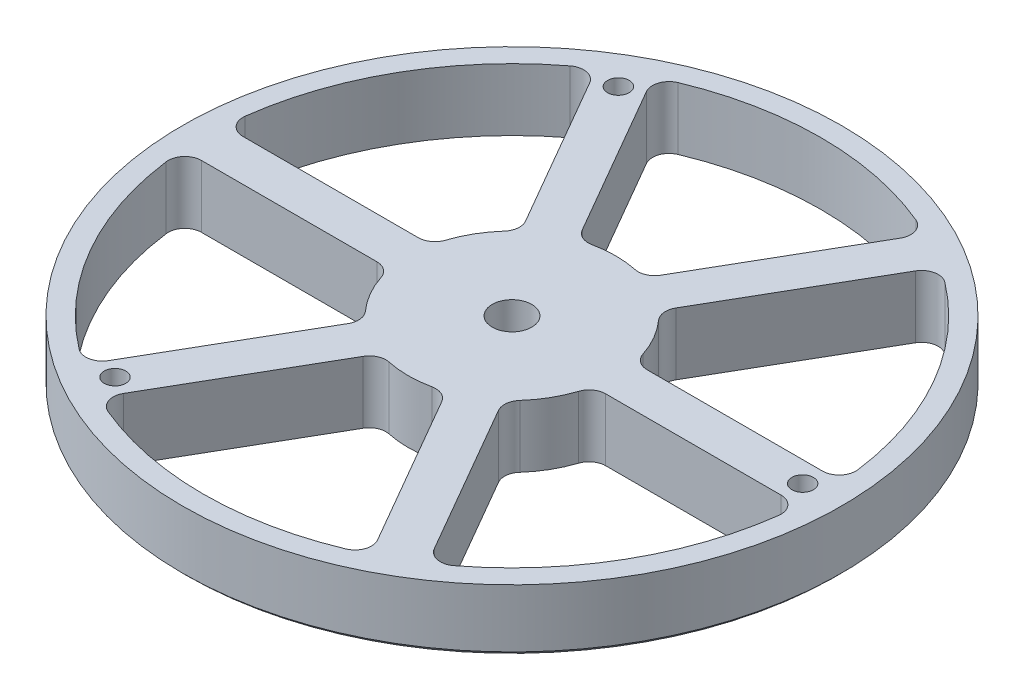
SolidWorks part; units mm, degrees
material "6061-T6 (SS)"
ref_plane "Front Plane" through (0, 0, 0) normal (0, 0, 1) x (1, 0, 0)
ref_plane "Top Plane" through (0, 0, 0) normal (0, 1, 0) x (1, 0, 0)
ref_plane "Right Plane" through (0, 0, 0) normal (1, 0, 0) x (0, 0, -1)
sketch "Sketch2" plane through (0, 0, 0) normal (1, 0, 0) x (0, 0, -1)
  line L0 (0, 0) -> (-79.375, 0)
  line L1 (-79.375, 0) -> (-79.375, 15)
  line L2 (-79.375, 15) -> (0, 15)
  line L5 (0, 15) -> (0, 0)
  dimension "D1" = 79.375
  dimension "D2" = 15
ref_axis "Axis1" through (0, -0.75, 0) along (0, 1, 0)
revolve "Revolve1" add sketch "Sketch2" angle 360 about axis through (0, -0.75, 0) along (0, 1, 0)
hole_wizard "#6 (0.204) Diameter Hole1" positions "Sketch6" profile "Sketch7" hole size "#6" standard "ANSI Inch" end condition through all
sketch "Sketch6" plane through (0, 15, 0) normal (0, 1, 0) x (1, 0, 0)
  line L0 (0, 0) -> (-69.8201, 120.932) construction
  line L2 (0, 0) -> (0, 109.0908) construction
  point P0 (-35, 60.6218)
  dimension "D1" = 30
  dimension "D2" = 70
sketch "Sketch7" plane through (-35, 15, -60.6218) normal (1, 0, 0) x (0, 0, 1)
  line L0 (0, 0) -> (0, 15)
  line L1 (0, 15) -> (2.5908, 15)
  line L2 (2.5908, 15) -> (2.5908, 0)
  line L5 (2.5908, 0) -> (0, 0)
  line L11 (0, -6.35) -> (0, 107.95) construction
  dimension "Thru Hole Dia." = 5.1816
  dimension "Thru Hole Depth" = 15
pattern_circular "CirPattern3" count 3 over 360 about axis through (0, -0.75, 0) along (0, 1, 0) of "#6 (0.204) Diameter Hole1"
sketch "Sketch8" plane through (0, 15, 0) normal (0, 1, 0) x (1, 0, 0)
  line L4 (0, 0) -> (0, 93.9995) construction
  line L5 (0, 0) -> (113.8372, 0) construction
  line L6 (-7.9173, 23.7132) -> (-32.7732, 66.7649)
  line L7 (7.9173, 23.7132) -> (32.7732, 66.7649)
  line L8 (0, 0) -> (-35, 60.6218) construction
  arc A0 (-7.9173, 23.7132) -> (7.9173, 23.7132) centre (0, 0) cw
  arc A1 (-32.7732, 66.7649) -> (32.7732, 66.7649) centre (0, 0) cw
  circle A2 centre (0, 0) radius 79.375 construction
  dimension "D1" = 25
  dimension "D2" = 5
  dimension "D3" = 5
extrude "Cut-Extrude1" cut sketch "Sketch8" against normal through all
fillet "Fillet1" radius 4 4 edges at (7.9173, 7.5, -23.7132) (32.7732, 7.5, -66.7649) (-7.9173, 7.5, -23.7132) (-32.7732, 7.5, -66.7649)
pattern_circular "CirPattern4" count 6 over 360 about axis through (0, -0.75, 0) along (0, 1, 0) of "Cut-Extrude1", "Fillet1"
chamfer "Chamfer2" distance 1 angle 45 1 edges at (0, 0, -79.375)
hole_wizard "3/8 (0.375) Diameter Hole1" positions "Sketch9" profile "Sketch11" hole size "3/8" standard "ANSI Inch" end condition through all
sketch "Sketch9" plane through (0, 0, 0) normal (0, -1, 0) x (-1, 0, 0)
  point P0 (0, 0)
sketch "Sketch11" plane through (0, 0, 0) normal (1, 0, 0) x (0, 0, -1)
  line L0 (0, 0) -> (0, 15)
  line L1 (0, 15) -> (4.7625, 15)
  line L2 (4.7625, 15) -> (4.7625, 0)
  line L5 (4.7625, 0) -> (0, 0)
  line L11 (0, -6.35) -> (0, 107.95) construction
  dimension "Thru Hole Dia." = 9.525
  dimension "Thru Hole Depth" = 15
equation "\"TubeDiameter\" = 6.250in"
equation "\"D1@Sketch2\"=\"TubeDiameter\"/2"
